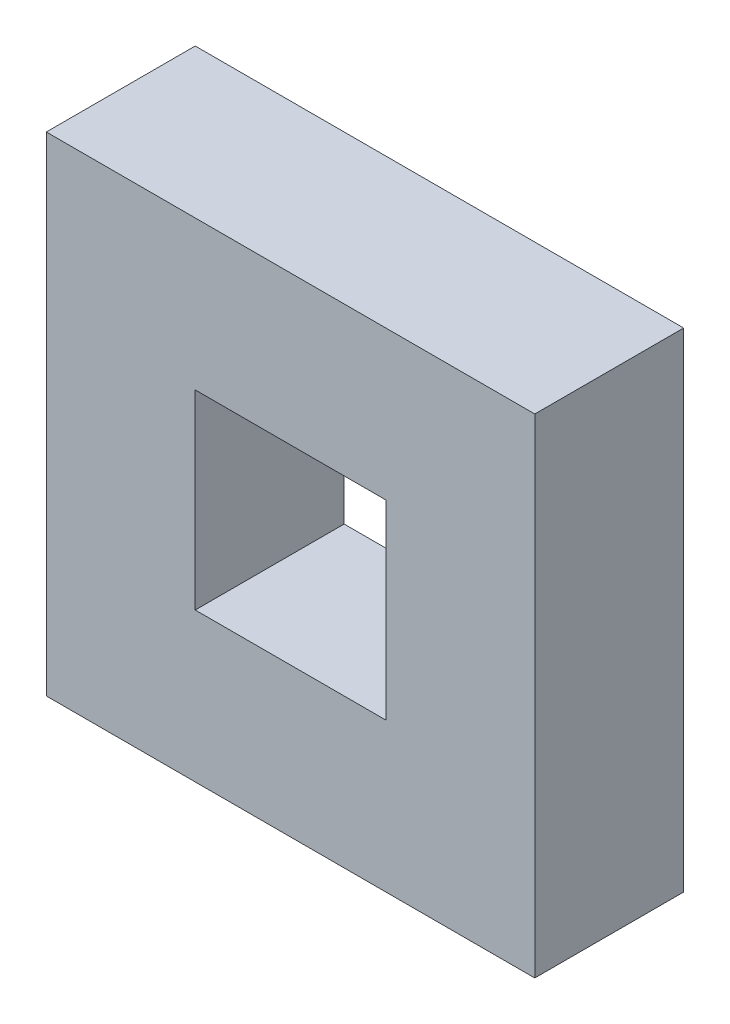
SolidWorks part; units mm, degrees
material "Balsa"
ref_plane "Front Plane" through (0, 0, 0) normal (0, 0, 1) x (1, 0, 0)
ref_plane "Top Plane" through (0, 0, 0) normal (0, 1, 0) x (1, 0, 0)
ref_plane "Right Plane" through (0, 0, 0) normal (1, 0, 0) x (0, 0, -1)
sketch "Sketch1" plane through (0, 0, 0) normal (0, 0, 1) x (1, 0, 0)
  line L0 (0, 0) -> (0, 20.828)
  line L6 (20.828, 20.828) -> (20.828, 0)
  line L7 (20.828, 0) -> (0, 0)
  line L8 (6.35, 6.35) -> (14.478, 6.35)
  line L9 (6.35, 6.35) -> (6.35, 14.478)
  line L10 (6.35, 14.478) -> (14.478, 14.478)
  line L11 (14.478, 6.35) -> (14.478, 14.478)
  line L12 (20.828, 20.828) -> (0, 20.828)
  point P13 (10.414, 0)
  dimension "D2" = 8.128
  dimension "D3" = 8.128
  dimension "D4" = 6.35
  dimension "D5" = 6.35
  dimension "D6" = 6.35
  dimension "D1" = 6.35
extrude "Boss-Extrude1" add sketch "Sketch1" along normal blind 6.35
equation "\"D1@Sketch1\"=\"D5@Sketch1\""
equation "\"D6@Sketch1\"=\"D5@Sketch1\""
equation "\"D4@Sketch1\"=\"D5@Sketch1\""
